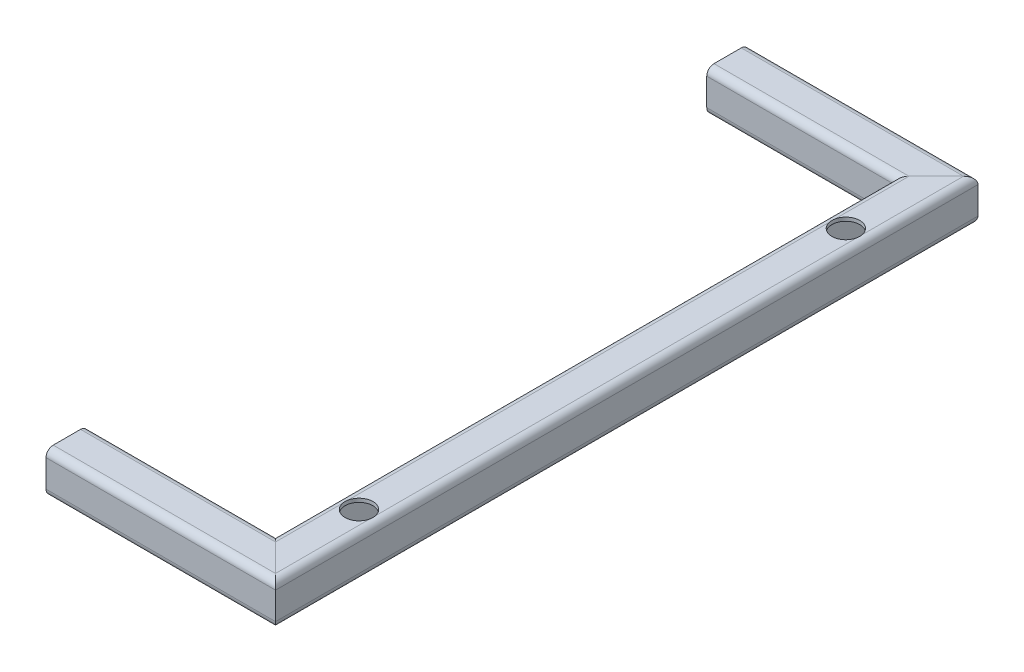
SolidWorks part; units mm, degrees
ref_plane "Front Plane" through (0, 0, 0) normal (0, 0, 1) x (1, 0, 0)
ref_plane "Top Plane" through (0, 0, 0) normal (0, 1, 0) x (1, 0, 0)
ref_plane "Right Plane" through (0, 0, 0) normal (1, 0, 0) x (0, 0, -1)
sketch "Sketch1" plane through (0, 0, 0) normal (0, 1, 0) x (1, 0, 0)
  line L0 (0, -20.8994) -> (0, 454.1006)
  line L1 (0, 454.1006) -> (-150, 454.1006)
  line L2 (0, -20.8994) -> (-150, -20.8994)
  dimension "D1" = 475
  dimension "D2" = 150
  dimension "D3" = 150
other "Structural Member1" corner treatment miter
ref_plane "Plane1" through (0, 0, 20.8994) normal (0, 0, -1) x (-1, 0, 0)
sketch "Sketch11" plane through (0, 0, 20.8994) normal (0, 0, -1) x (-1, 0, 0)
  line L0 (-9.8, -12.4) -> (9.8, -12.4)
  line L1 (-12.4, -9.8) -> (-12.4, 9.8)
  line L2 (9.8, 12.4) -> (-9.8, 12.4)
  line L3 (12.4, 9.8) -> (12.4, -9.8)
  line L4 (-9.8, -15) -> (9.8, -15)
  line L5 (-15, -9.8) -> (-15, 9.8)
  line L6 (9.8, 15) -> (-9.8, 15)
  line L7 (15, 9.8) -> (15, -9.8)
  arc A0 (15, 9.8) -> (9.8, 15) centre (9.8, 9.8) ccw
  arc A1 (9.8, -15) -> (15, -9.8) centre (9.8, -9.8) ccw
  arc A2 (-15, -9.8) -> (-9.8, -15) centre (-9.8, -9.8) ccw
  arc A3 (-9.8, 15) -> (-15, 9.8) centre (-9.8, 9.8) ccw
  arc A4 (-9.8, 12.4) -> (-12.4, 9.8) centre (-9.8, 9.8) ccw
  arc A5 (12.4, 9.8) -> (9.8, 12.4) centre (9.8, 9.8) ccw
  arc A6 (9.8, -12.4) -> (12.4, -9.8) centre (9.8, -9.8) ccw
  arc A7 (-12.4, -9.8) -> (-9.8, -12.4) centre (-9.8, -9.8) ccw
  point P0 (-15, 0)
  point P1 (15, 0)
  point P2 (0, 15)
  point P3 (0, -15)
  point P4 (0, 0)
  point P5 (-15, -15)
  point P6 (15, -15)
  point P7 (15, 15)
  point P8 (-15, 15)
  point P33 (0, 0)
  dimension "D1" = 5.2
  dimension "Thickness" = 2.6
  dimension "V_leg" = 30
sketch "Sketch12" plane through (0, 15, 0) normal (0, 1, 0) x (1, 0, 0)
  line L3 (15, -35.8994) -> (-150, -35.8994) construction
  circle A0 centre (0, 39.1006) radius 10
  circle A1 centre (0, 389.1006) radius 10
  point P6 (-16.0825, -32.9588)
  dimension "D1" = 20
  dimension "D2" = 20
  dimension "D3" = 75
  dimension "D4" = 350
extrude "Cut-Extrude1" cut sketch "Sketch12" against normal blind 45
